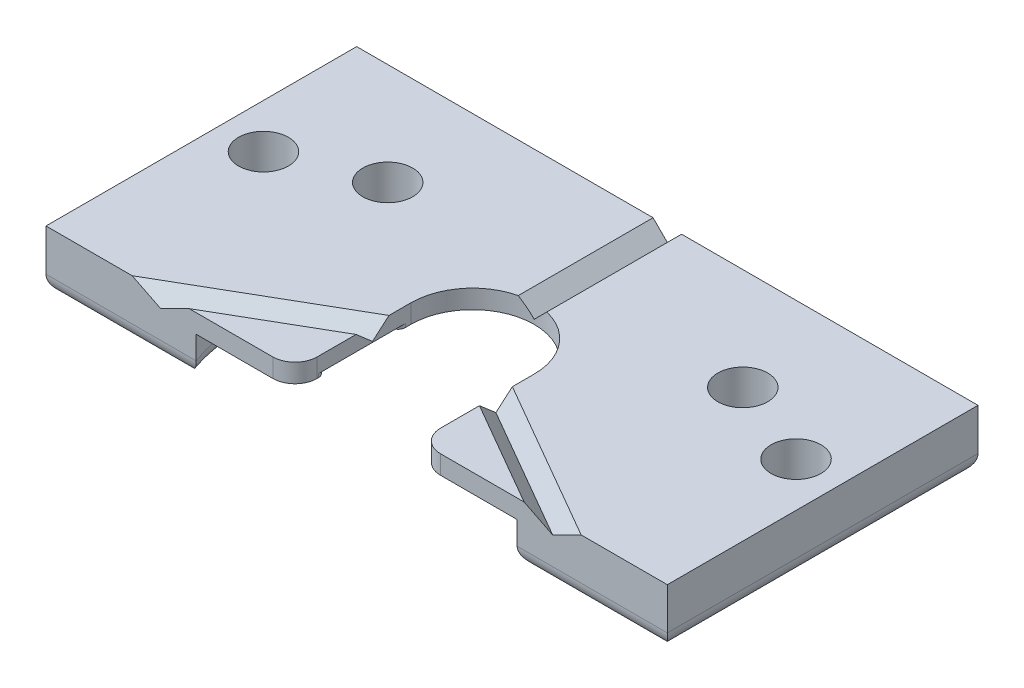
SolidWorks part; units mm, degrees
ref_plane "Front Plane" through (0, 0, 0) normal (0, 0, 1) x (1, 0, 0)
ref_plane "Top Plane" through (0, 0, 0) normal (0, 1, 0) x (1, 0, 0)
ref_plane "Right Plane" through (0, 0, 0) normal (1, 0, 0) x (0, 0, -1)
sketch "Sketch1" plane through (0, 0, 0) normal (0, 1, 0) x (1, 0, 0)
  line L0 (-8.8265, 4.5085) -> (-8.8265, -12.065)
  line L1 (-44.45, -12.065) -> (-8.8265, -12.065)
  line L2 (-44.45, -12.065) -> (-44.45, 32.385)
  line L3 (-44.45, 32.385) -> (44.45, 32.385)
  line L4 (44.45, -12.065) -> (44.45, 32.385)
  line L5 (-44.45, -12.065) -> (44.45, 32.385) construction
  line L6 (-44.45, 32.385) -> (44.45, -12.065) construction
  line L7 (8.8265, 4.5085) -> (8.8265, -12.065)
  line L11 (8.8265, -12.065) -> (44.45, -12.065)
  arc A0 (-8.8265, 4.5085) -> (8.8265, 4.5085) centre (0, 4.5085) cw
  point P0 (0, 10.16)
  point P13 (0, 32.385)
  point P15 (0, 13.335)
  dimension "D6" = 8.8265
  dimension "D4" = 19.05
  dimension "D1" = 10.16
  dimension "D2" = 44.45
  dimension "D3" = 88.9
extrude "Boss-Extrude1" add sketch "Sketch1" along normal blind 3.175 contours L1 L0 A0 L7 L11 L4 L3 L2
sketch "Sketch3" plane through (0, 3.175, 0) normal (0, 1, 0) x (1, 0, 0)
  line L0 (0, 13.335) -> (0, 32.385) construction
  line L1 (-44.45, 32.385) -> (44.45, 32.385) construction
  line L2 (-2.54, 41.5161) -> (-2.54, 9.7661)
  line L3 (-2.54, 9.7661) -> (2.54, 9.7661)
  line L4 (2.54, 9.7661) -> (2.54, 41.5161)
  line L5 (2.54, 41.5161) -> (-2.54, 41.5161)
  arc A0 (8.8265, 4.5085) -> (-8.8265, 4.5085) centre (0, 4.5085) ccw construction
  point P9 (0, 9.7661)
  dimension "D1" = 5.08
  dimension "D2" = 31.75
extrude "Cut-Extrude1" cut sketch "Sketch3" against normal blind 3.175 draft 45
sketch "Sketch4" plane through (0, 0, 0) normal (1, 0, 0) x (0, 0, -1)
  line L0 (4.1252, 0) -> (4.1252, 18.8814)
pattern_circular "CirPattern1" count 3 over 360 about axis through (0, 0, -4.1252) along (0, 1, 0) of "Cut-Extrude1" reverse direction yes
sketch "Sketch2" plane through (0, 0, 0) normal (0, 1, 0) x (1, 0, 0)
  line L0 (-8.8265, 1.0916) -> (-8.8265, -13.8458)
  line L1 (8.8265, 1.0916) -> (8.8265, -13.8458)
  line L2 (-13.6664, -2.4806) -> (-1.3362, 18.876)
  line L3 (1.4178, 18.876) -> (13.748, -2.4806)
  line L4 (12.371, -4.8656) -> (-12.2894, -4.8656)
  arc A0 (-8.8265, 1.0916) -> (8.8265, 1.0916) centre (0, 1.0916) cw
  arc A1 (13.748, -2.4806) -> (12.371, -4.8656) centre (12.371, -3.2756) cw
  arc A2 (-13.6664, -2.4806) -> (-12.2894, -4.8656) centre (-12.2894, -3.2756) ccw
  arc A3 (-1.3362, 18.876) -> (1.4178, 18.876) centre (0.0408, 18.081) cw
  point P0 (0.0408, 11.5542)
  dimension "D1" = 1.59
  dimension "D2" = 8.8265
sketch "Sketch5" plane through (0, 0, 0) normal (0, -1, 0) x (1, 0, 0)
  line L1 (-5.1662, -13.843) -> (5.2478, -13.843)
  line L2 (-5.1662, -13.843) -> (-5.1662, -24.257)
  line L3 (-5.1662, -24.257) -> (5.2478, -24.257)
  line L4 (5.2478, -13.843) -> (5.2478, -24.257)
  line L5 (-5.1662, -13.843) -> (5.2478, -24.257) construction
  line L6 (-5.1662, -24.257) -> (5.2478, -13.843) construction
  point P0 (0.0408, -16.8423)
  point P8 (0.0408, -19.05)
  dimension "D1" = 10.414
  dimension "D2" = 19.05
extrude "Cut-Extrude2" cut sketch "Sketch5" against normal blind 0.508
pattern_circular "CirPattern2" count 3 over 360 about axis through (0, 0, -4.1252) along (0, 1, 0) of "Cut-Extrude2"
fillet "Fillet1" radius 3.175 2 edges at (8.8265, 1.5875, 12.065) (-8.8265, 1.5875, 12.065)
sketch "Sketch6" plane through (0, 0.508, 0) normal (0, -1, 0) x (1, 0, 0)
  line L11 (-44.45, 12.065) -> (-44.45, -32.385)
  line L12 (-44.45, 12.065) -> (-22.9623, 12.065)
  line L13 (0, -10.3848) -> (0, 10.3848) construction
  line L14 (-44.45, -32.385) -> (44.45, -32.385) construction
  line L15 (44.45, 12.065) -> (44.45, -32.385) construction
  line L16 (19.05, -32.385) -> (44.45, -32.385)
  line L19 (44.45, -32.385) -> (44.45, -6.985)
  line L24 (-44.45, -32.385) -> (19.05, -32.385)
  line L26 (12.0015, 12.065) -> (44.45, 12.065) construction
  line L27 (22.9623, 12.065) -> (44.45, 12.065)
  line L28 (44.45, 12.065) -> (44.45, -6.985)
  arc A0 (-22.9623, 12.065) -> (0, -26.035) centre (4.0019, 2.3464) ccw
  arc A2 (22.9623, 12.065) -> (0, -26.035) centre (-4.0019, 2.3464) cw
extrude "Boss-Extrude2" add sketch "Sketch6" along normal blind 6.35
fillet "Fillet2" radius 2.54 7 edges at (44.45, -5.842, -10.16) (33.7062, -5.842, 12.065) (-20.5466, -5.842, -12.4486) (20.5466, -5.842, -12.4486) (0, -5.842, -32.385) (-44.45, -5.842, -10.16) (-33.7062, -5.842, 12.065)
sketch "Sketch7" plane through (0, -5.842, 0) normal (0, -1, 0) x (1, 0, 0)
  line L0 (-38.1, -12.7) -> (38.1, -12.7) construction
  line L1 (-25.4, -17.78) -> (25.4, -17.78) construction
  circle A0 centre (-38.1, -12.7) radius 3.5687
  circle A1 centre (38.1, -12.7) radius 3.5687
  circle A2 centre (-25.4, -17.78) radius 3.5687
  circle A3 centre (25.4, -17.78) radius 3.5687
  point P2 (0, -12.7)
  point P10 (0, -17.78)
  dimension "D3" = 7.1374
  dimension "D4" = 7.1374
  dimension "D6" = 7.1374
  dimension "D7" = 17.78
  dimension "D1" = 76.2
  dimension "D2" = 12.7
  dimension "D5" = 50.8
extrude "Cut-Extrude3" cut sketch "Sketch7" against normal through all
sketch "Sketch8" plane through (-44.45, 0, 0) normal (-1, 0, 0) x (0, 0, 1)
  line L0 (12.065, 3.175) -> (12.065, -3.302) construction
  line L1 (-32.385, 3.175) -> (12.065, 3.175)
  line L2 (-32.385, 3.175) -> (-32.385, 2.675)
  line L3 (-32.385, 2.675) -> (12.065, 2.675)
  line L4 (12.065, 3.175) -> (12.065, 2.675)
  line L5 (-32.385, 3.175) -> (12.065, 2.675) construction
  line L6 (-32.385, 2.675) -> (12.065, 3.175) construction
  point P4 (-10.16, 2.925)
  dimension "D1" = 0.5
extrude "Cut-Extrude4" cut sketch "Sketch8" against normal through all
fillet "Fillet3" radius 1.016 12 edges at (-5.1662, 0.254, -24.257) (14.8107, 0.254, 10.4854) (20.0177, 0.254, 1.4666) (-14.8515, 0.254, 10.4147) (-20.0585, 0.254, 1.3959) (-11.0397, 0.254, -3.8111) (8.8265, 0.254, 7.0304) (-8.8265, 0.254, 6.9362) (8.8265, 0.254, 0.0223) (5.2478, 0.254, -13.843) (-5.1662, 0.254, -13.843) (5.2478, 0.254, -24.257)
fillet "Fillet4" radius 1.016 2 edges at (10.9989, 0.254, -3.7404) (-8.8265, 0.254, 0.0223)
sketch "Sketch9" plane through (0, 0, 0) normal (0, -1, 0) x (1, 0, 0)
  line L1 (4.9502, -23.9594) -> (-4.8686, -23.9594)
  line L2 (4.9502, -23.9594) -> (4.9502, -14.1406)
  line L3 (4.9502, -14.1406) -> (-4.8686, -14.1406)
  line L4 (-4.8686, -23.9594) -> (-4.8686, -14.1406)
  line L5 (4.9502, -23.9594) -> (-4.8686, -14.1406) construction
  line L6 (4.9502, -14.1406) -> (-4.8686, -23.9594) construction
  arc A0 (-4.1502, -13.843) -> (-5.1662, -14.859) centre (-4.1502, -14.859) ccw construction
  arc A1 (5.2478, -14.859) -> (4.2318, -13.843) centre (4.2318, -14.859) ccw construction
  arc A2 (4.2318, -24.257) -> (5.2478, -23.241) centre (4.2318, -23.241) ccw construction
  point P0 (0.0408, -19.05)
  point P6 (0, 0)
  point P7 (-4.4876, -14.5216)
  point P11 (4.5692, -14.5216)
  point P15 (0, 0)
